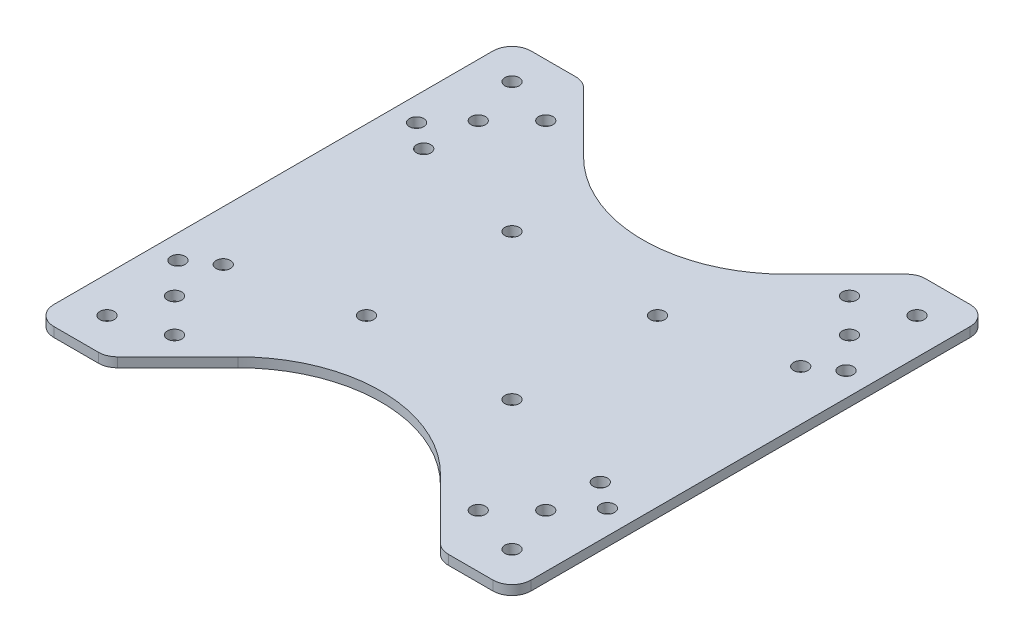
SolidWorks part; units mm, degrees
other "标注1"
sketch "草图9" plane through (-50, 0, -50) normal (0, -1, 0) x (1, 0, 0)
material "Thornel Mat VMA"
ref_plane "前视基准面" through (0, 0, 0) normal (0, 0, 1) x (1, 0, 0)
ref_plane "上视基准面" through (0, 0, 0) normal (0, 1, 0) x (1, 0, 0)
ref_plane "右视基准面" through (0, 0, 0) normal (1, 0, 0) x (0, 0, -1)
other "Configuration Table"
sketch "草图1" plane through (0, 0, 0) normal (0, 1, 0) x (1, 0, 0)
  line L1 (-50, -50) -> (50, -50)
  line L2 (-50, -50) -> (-50, 50)
  line L3 (-50, 50) -> (50, 50)
  line L4 (50, -50) -> (50, 50)
  line L5 (-50, -50) -> (50, 50) construction
  line L6 (-50, 50) -> (50, -50) construction
  point P0 (0, 0)
  dimension "D1" = 100
  dimension "D2" = 100
extrude "凸台-拉伸1" add sketch "草图1" along normal blind 2
sketch "草图3" plane through (0, 2, 0) normal (0, 1, 0) x (1, 0, 0)
  line L0 (-1000, 0) -> (49000, 0) construction
  line L1 (-42.4264, 42.4264) -> (0, 0) construction
  line L2 (-42.9749, 27.7358) -> (35312.3642, 35383.0749) construction
  line L3 (0, -1000) -> (0, 49000) construction
  circle A0 centre (0, 0) radius 60 construction
  circle A1 centre (-42.4264, 42.4264) radius 1.5
  circle A2 centre (-31.8198, 38.8909) radius 1.5
  circle A3 centre (-38.8909, 31.8198) radius 1.5
  circle A4 centre (-31.8198, -38.8909) radius 1.5
  circle A5 centre (-38.8909, -31.8198) radius 1.5
  circle A6 centre (-42.4264, -42.4264) radius 1.5
  circle A7 centre (31.8198, 38.8909) radius 1.5
  circle A8 centre (38.8909, 31.8198) radius 1.5
  circle A9 centre (42.4264, 42.4264) radius 1.5
  circle A10 centre (31.8198, -38.8909) radius 1.5
  circle A11 centre (42.4264, -42.4264) radius 1.5
  circle A12 centre (38.8909, -31.8198) radius 1.5
  dimension "D1" = 120
  dimension "D3" = 3
  dimension "D6" = 3
  dimension "D7" = 3
  dimension "D8" = 5
  dimension "D9" = 5
  dimension "D2" = 45
  dimension "D4" = 90
  dimension "D5" = 10
extrude "切除-拉伸2" cut sketch "草图3" against normal through all
sketch "草图4" plane through (0, 0, 0) normal (0, -1, 0) x (1, 0, 0)
  line L0 (0, -1000) -> (0, 49000) construction
  line L1 (-1000, 0) -> (49000, 0) construction
  circle A0 centre (-39.5, 21) radius 1.5
  circle A1 centre (39.5, 21) radius 1.5
  circle A2 centre (39.5, -21) radius 1.5
  circle A3 centre (-39.5, -21) radius 1.5
  dimension "D1" = 21
  dimension "D2" = 39.5
  dimension "D3" = 3
extrude "切除-拉伸3" cut sketch "草图4" against normal through all
sketch "草图5" plane through (0, 0, 0) normal (0, -1, 0) x (1, 0, 0)
  line L0 (-50, -50) -> (-50, 50) construction
  line L1 (-47, -20) -> (-45, -20)
  line L2 (-47, -20) -> (-47, 20)
  line L3 (-47, 20) -> (-45, 20)
  line L4 (-45, -20) -> (-45, 20)
  line L5 (-47, -20) -> (-45, 20) construction
  line L6 (-47, 20) -> (-45, -20) construction
  line L7 (0, -1000) -> (0, 49000) construction
  line L8 (47, 20) -> (45, 20)
  line L9 (45, -20) -> (45, 20)
  line L10 (47, -20) -> (45, -20)
  line L11 (47, -20) -> (47, 20)
  point P0 (-46, 0)
  dimension "D1" = 40
  dimension "D2" = 2
  dimension "D3" = 3
  dimension "D4" = 0
sketch "草图6" plane through (0, 0, 0) normal (0, -1, 0) x (1, 0, 0)
  line L0 (-1000, 0) -> (49000, 0) construction
  line L1 (-35, 50) -> (0, 15)
  line L2 (-50, 50) -> (50, 50) construction
  line L3 (0, 15) -> (35, 50)
  line L4 (35, 50) -> (-35, 50)
  line L5 (0, -15) -> (35, -50)
  line L6 (-35, -50) -> (0, -15)
  line L7 (35, -50) -> (-35, -50)
  dimension "D3" = 0
  dimension "D1" = 45
  dimension "D2" = 45
  dimension "D4" = 70
extrude "切除-拉伸6" cut sketch "草图6" against normal through all
fillet "圆角2" radius 30 2 edges at (0, 1, -15) (0, 1, 15)
sketch "草图7" plane through (0, 0, 0) normal (0, -1, 0) x (1, 0, 0)
  circle A0 centre (-15.25, 15.25) radius 1.5
  circle A1 centre (15.25, 15.25) radius 1.5
  circle A2 centre (15.25, -15.25) radius 1.5
  circle A3 centre (-15.25, -15.25) radius 1.5
  point P12 (0, 0)
  dimension "D1" = 15.25
  dimension "D2" = 3
  dimension "D3" = 15.25
  dimension "D4" = 4
extrude "切除-拉伸7" cut sketch "草图7" against normal through all
sketch "草图8" plane through (0, 0, 0) normal (0, -1, 0) x (1, 0, 0)
  line L0 (-1000, 0) -> (49000, 0) construction
  line L1 (0, -1000) -> (0, 49000) construction
  line L2 (-50, -50) -> (-50, 50) construction
  circle A0 centre (-45, 25) radius 1.5
  circle A1 centre (-45, -25) radius 1.5
  circle A2 centre (45, -25) radius 1.5
  circle A3 centre (45, 25) radius 1.5
  dimension "D1" = 3
  dimension "D2" = 5
  dimension "D3" = 25
extrude "切除-拉伸8" cut sketch "草图8" against normal through all
fillet "圆角3" radius 4 8 edges at (35, 1, 50) (50, 1, 50) (50, 1, -50) (35, 1, -50) (-35, 1, -50) (-50, 1, -50) (-35, 1, 50) (-50, 1, 50)
